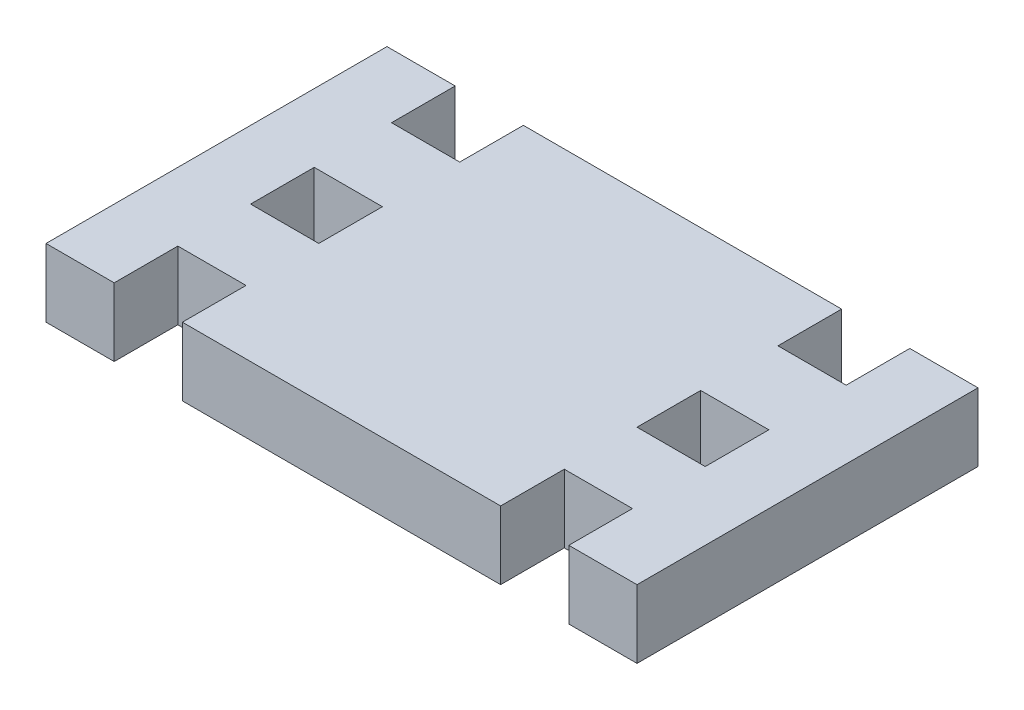
SolidWorks part; units mm, degrees
ref_plane "Front Plane" through (0, 0, 0) normal (0, 0, 1) x (1, 0, 0)
ref_plane "Top Plane" through (0, 0, 0) normal (0, 1, 0) x (1, 0, 0)
ref_plane "Right Plane" through (0, 0, 0) normal (1, 0, 0) x (0, 0, -1)
sketch "Sketch1" plane through (0, 0, 0) normal (0, 1, 0) x (1, 0, 0)
  line L0 (-10, -6.9776) -> (-7, -6.9776)
  line L5 (-7, -9.7776) -> (7, -9.7776)
  line L11 (-7, 5.2224) -> (7, 5.2224)
  line L30 (-7.5, -7.5) -> (7.5, 7.5) construction
  line L35 (-7.5, 7.5) -> (7.5, -7.5) construction
  line L45 (-10, 2.4224) -> (-7, 2.4224)
  line L46 (-7, 5.2224) -> (-7, 2.4224)
  line L48 (-7, -6.9776) -> (-7, -9.7776)
  line L50 (-10, -0.9776) -> (-7, -0.9776)
  line L52 (-10, -3.7776) -> (-7, -3.7776)
  line L53 (-7, -0.9776) -> (-7, -3.7776)
  line L54 (0, 5.2224) -> (0, -9.7776) construction
  line L55 (7, -0.9776) -> (7, -3.7776)
  line L56 (10, -3.7776) -> (7, -3.7776)
  line L57 (10, -0.9776) -> (7, -0.9776)
  line L59 (7, -6.9776) -> (7, -9.7776)
  line L60 (7, 5.2224) -> (7, 2.4224)
  line L61 (10, 2.4224) -> (7, 2.4224)
  line L63 (10, -6.9776) -> (7, -6.9776)
  line L64 (10, -0.9776) -> (10, -3.7776)
  line L65 (10, 5.2224) -> (13, 5.2224)
  line L66 (10, 5.2224) -> (10, 2.4224)
  line L67 (10, -9.7776) -> (13, -9.7776)
  line L68 (13, 5.2224) -> (13, -9.7776)
  line L69 (10, -6.9776) -> (10, -9.7776)
  line L70 (-10, -0.9776) -> (-10, -3.7776)
  line L71 (-13, 5.2224) -> (-10, 5.2224)
  line L72 (-13, 5.2224) -> (-13, -9.7776)
  line L73 (-13, -9.7776) -> (-10, -9.7776)
  line L74 (-10, 5.2224) -> (-10, 2.4224)
  line L75 (-10, -6.9776) -> (-10, -9.7776)
  point P0 (0, 0)
  dimension "D3" = 3
  dimension "D1" = 15
  dimension "D2" = 3
  dimension "D4" = 2.8
  dimension "D5" = 2.8
  dimension "D6" = 14
  dimension "D7" = 3
  dimension "D8" = 2.8
  dimension "D9" = 3.4
  dimension "D10" = 15
  dimension "D11" = 0
  dimension "D12" = 3
  dimension "D13" = 15
  dimension "D14" = 0
  dimension "D15" = 20
  dimension "D16" = 3.2
extrude "Boss-Extrude1" add sketch "Sketch1" along normal blind 3
